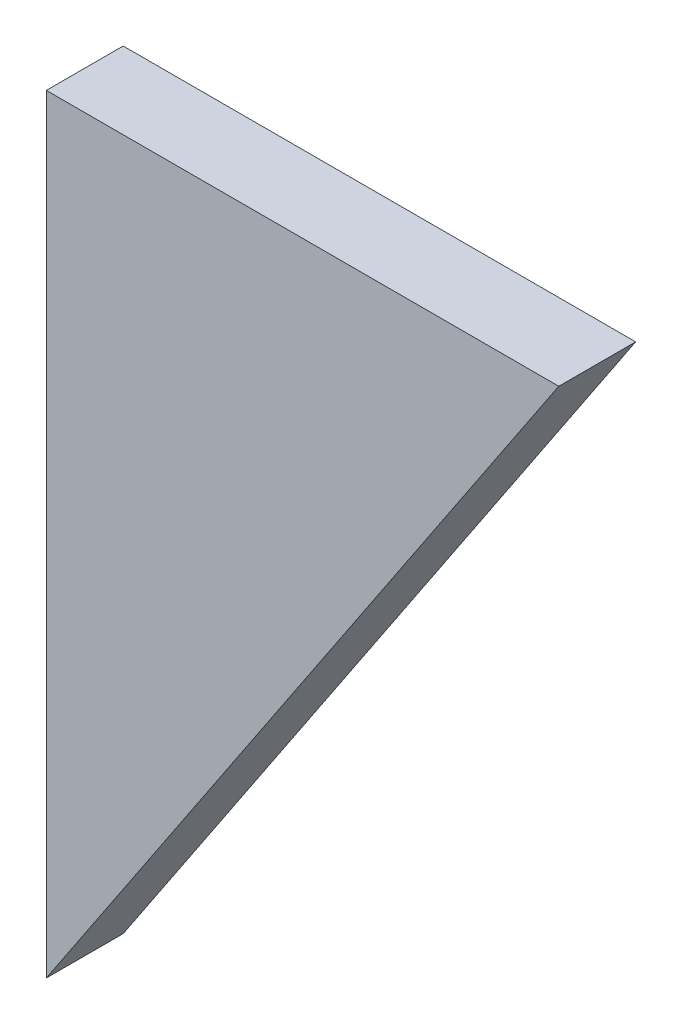
SolidWorks part; units mm, degrees
material "Plain Carbon Steel"
ref_plane "Front Plane" through (0, 0, 0) normal (0, 0, 1) x (1, 0, 0)
ref_plane "Top Plane" through (0, 0, 0) normal (0, 1, 0) x (1, 0, 0)
ref_plane "Right Plane" through (0, 0, 0) normal (1, 0, 0) x (0, 0, -1)
sketch "Sketch1" plane through (0, 0, 0) normal (0, 0, 1) x (1, 0, 0)
  line L0 (0, 0) -> (0, -60)
  line L1 (0, -55) -> (0, 55) construction
  line L2 (0, -60) -> (40, 0)
  line L3 (55, 0) -> (-55, 0) construction
  line L4 (40, 0) -> (0, 0)
  dimension "D1" = 60
  dimension "D2" = 40
extrude "Boss-Extrude1" add sketch "Sketch1" along normal mid plane 6
